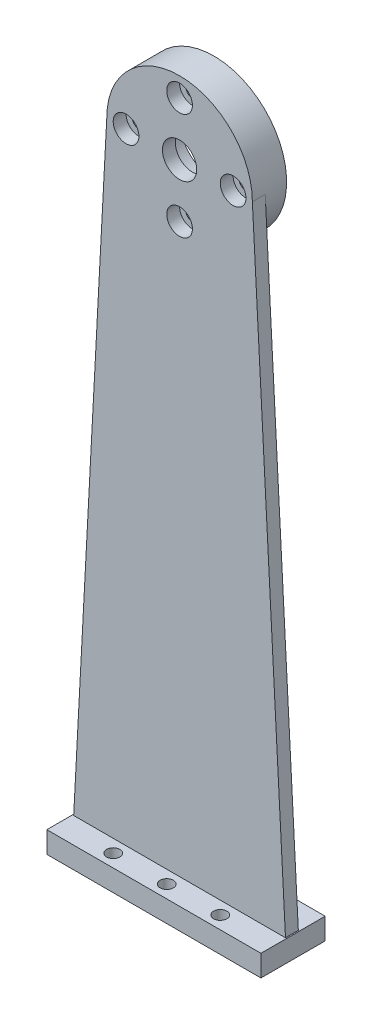
SolidWorks part; units mm, degrees
ref_plane "Front Plane" through (0, 0, 0) normal (0, 0, 1) x (1, 0, 0)
ref_plane "Top Plane" through (0, 0, 0) normal (0, 1, 0) x (1, 0, 0)
ref_plane "Right Plane" through (0, 0, 0) normal (1, 0, 0) x (0, 0, -1)
sketch "Sketch1" plane through (0, 0, 0) normal (0, 0, 1) x (1, 0, 0)
  line L0 (-25, 0) -> (25, 0)
  line L1 (0, 0) -> (0, 150) construction
  line L2 (-17, 150) -> (-25, 0)
  line L3 (25, 0) -> (17, 150)
  circle A0 centre (0, 150) radius 4
  arc A1 (-17, 150) -> (17, 150) centre (0, 150) cw
  point P4 (0, 0)
extrude "Boss-Extrude1" add sketch "Sketch1" along normal blind 3
sketch "Sketch2" plane through (0, 0, 0) normal (0, 0, -1) x (-1, 0, 0)
  circle A0 centre (0, 150) radius 17
  circle A1 centre (0, 150) radius 8
extrude "Boss-Extrude2" add sketch "Sketch2" along normal blind 5
sketch "Sketch3" plane through (0, 0, 3) normal (0, 0, 1) x (1, 0, 0)
  circle A0 centre (0, 150) radius 12.5 construction
  circle A1 centre (-12.5, 150) radius 1.55
  circle A2 centre (0, 162.5) radius 1.55
  circle A3 centre (12.5, 150) radius 1.55
  circle A4 centre (0, 137.5) radius 1.55
  point P14 (0, 150)
  dimension "D1" = 4
extrude "Cut-Extrude1" cut sketch "Sketch3" against normal blind 8
sketch "Sketch4" plane through (0, 0, 3) normal (0, 0, 1) x (1, 0, 0)
  circle A0 centre (-12.5, 150) radius 3
  circle A1 centre (0, 162.5) radius 3
  circle A2 centre (12.5, 150) radius 3
  circle A3 centre (0, 137.5) radius 3
  point P12 (0, 150)
  dimension "D1" = 4
extrude "Cut-Extrude2" cut sketch "Sketch4" against normal blind 3
sketch "Sketch5" plane through (0, 0, 0) normal (0, -1, 0) x (1, 0, 0)
  line L3 (-25, -6) -> (-25, 9)
  line L5 (25, -6) -> (25, 9)
  line L7 (-25, 9) -> (25, 9)
  line L8 (25, -6) -> (-25, -6)
  circle A0 centre (-12.5, 6) radius 1.55
  circle A1 centre (0, 6) radius 1.55
  circle A2 centre (12.5, 6) radius 1.55
  circle A3 centre (0, -3) radius 1.55
  circle A4 centre (-12.5, -3) radius 1.55
  circle A5 centre (12.5, -3) radius 1.55
extrude "Boss-Extrude3" add sketch "Sketch5" against normal blind 5
